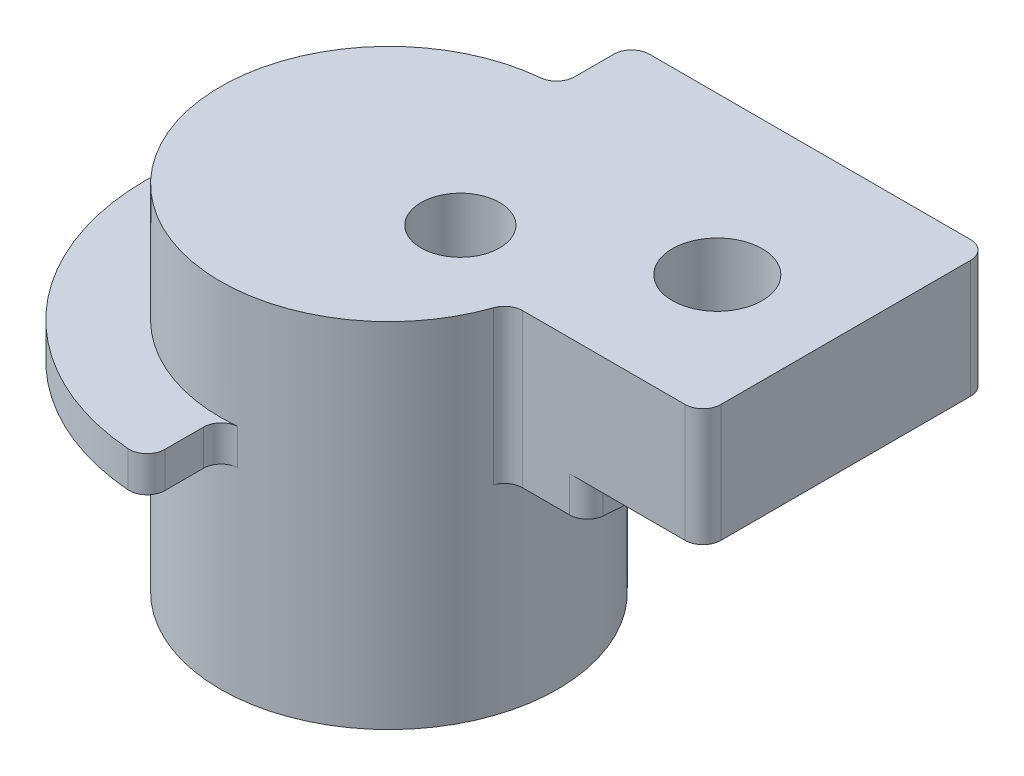
SolidWorks part; units mm, degrees
material "PET"
ref_plane "Front Plane" through (0, 0, 0) normal (1, 0, 0) x (0, 1, 0)
ref_plane "Top Plane" through (0, 0, 0) normal (0, 0, 1) x (0, 1, 0)
ref_plane "Right Plane" through (0, 0, 0) normal (0, 1, 0) x (-1, 0, 0)
sketch "Sketch2" plane through (0, 0, 0) normal (0, 0, 1) x (0, 1, 0)
  line L0 (0, 7.5) -> (0, -7.5) construction
  line L1 (15.7163, -7.5) -> (-15.7163, -7.5)
  line L2 (15.7163, -7.5) -> (15.7163, 7.5)
  line L3 (15.7163, 7.5) -> (-15.7163, 7.5)
  line L4 (-15.7163, -7.5) -> (-15.7163, 7.5)
  line L5 (15.7163, -7.5) -> (-15.7163, 7.5) construction
  line L6 (15.7163, 7.5) -> (-15.7163, -7.5) construction
  line L11 (-10.4775, 10.795) -> (-8.89, 10.795)
  line L12 (-10.4775, 10.795) -> (-10.4775, -10.795)
  line L19 (-10.4775, -10.795) -> (-8.89, -10.795)
  line L20 (-8.89, 10.795) -> (-8.89, -10.795)
  line L21 (10.4775, -10.795) -> (8.89, -10.795)
  line L22 (8.89, 10.795) -> (8.89, -10.795)
  line L23 (10.4775, 10.795) -> (8.89, 10.795)
  line L24 (10.4775, 10.795) -> (10.4775, -10.795)
  line L25 (-15.7163, 0) -> (15.7163, 0)
  point P0 (0, 0)
  point P6 (0, 0)
  point P11 (0, 0)
  point P16 (-10.4775, 0)
  dimension "D1" = 15
  dimension "D2" = 31.4325
  dimension "D5" = 1.5875
  dimension "D6" = 21.59
  dimension "D7" = 8.89
revolve "Revolve2" add sketch "Sketch2" angle 360 about L25 region at (-3.75, 13.0969, 0) region at (-3.75, 9.6838, 0) region at (-3.75, 0, 0) region at (-9.1475, 9.6838, 0) region at (-3.75, -9.6838, 0) region at (-3.75, -13.0969, 0) region at (-9.1475, -9.6838, 0)
sketch "Sketch3" plane through (0, 0, 0) normal (0, 1, 0) x (-1, 0, 0)
  circle A0 centre (0, 0) radius 11.3381
extrude "Cut-Extrude1" cut sketch "Sketch3" against normal blind 21.336
sketch "Sketch5" plane through (0, 15.7163, 0) normal (0, 1, 0) x (-1, 0, 0)
  line L5 (0, -10.795) -> (-15.875, -10.795)
  line L6 (0, -10.795) -> (0, 1.905)
  line L7 (0, 1.905) -> (-15.875, 1.905)
  line L8 (-15.875, -10.795) -> (-15.875, 1.905)
  circle A0 centre (-3.175, 0) radius 1.75
  circle A1 centre (0, 0) radius 7.5 construction
  circle A2 centre (0, 0) radius 7.5 construction
  circle A3 centre (-3.175, 0) radius 3.35 construction
  circle A9 centre (0, 0) radius 7.5
  circle A10 centre (-10.795, -3.81) radius 2
  circle A13 centre (0, 0) radius 10.795 construction
  circle A14 centre (-10.795, -3.81) radius 3.6 construction
  circle A15 centre (0, 0) radius 10.541 construction
  point P4 (7.5, 0)
  point P13 (-3.175, 1.75)
  point P15 (-3.175, 3.35)
  point P20 (-8.795, -3.81)
  point P21 (-7.195, -3.81)
  circle M7 centre (0, 0) radius 7.5
  dimension "D1" = 3.5
  dimension "D8" = 1.6
  dimension "D3" = 4
  dimension "D7" = 15.875
  dimension "D10" = 21.082
  dimension "D2" = 3.175
  dimension "D4" = 7.62
  dimension "D5" = 1.6
  dimension "D6" = 12.7
  dimension "D9" = 3.81
  dimension "5" = 0
extrude "Cut-Extrude3" cut sketch "Sketch5" against normal blind 27.432 contours A0 region at (3.175, 15.7163, 0)
extrude "Boss-Extrude2" add sketch "Sketch5<3>" against normal up to surface (5.2387 mm away) contours L8 A10 M7 region at (9.7265, 15.7163, -5.5154) up to face at (7.5, 10.4775, 0)
sketch "Sketch5<3>" plane through (0, 15.7163, 0) normal (0, 1, 0) x (-1, 0, 0) same geometry as "Sketch5"
fillet "Fillet1" radius 0.7937 5 edges at (0, 13.0969, -10.795) (0, 13.0969, -7.5) (15.875, 13.0969, -10.795) (7.254, 13.0969, 1.905) (15.875, 13.0969, 1.905)
sketch "Sketch6" plane through (0, 10.4775, 0) normal (0, 1, 0) x (-1, 0, 0)
  line L0 (0, 7.5) -> (0, 10.795)
  line L3 (0, -8.2557) -> (0, -10.0013)
  line L4 (-10.6256, 1.905) -> (-7.8424, 1.905)
  line L5 (0, -8.2557) -> (0, -10.0013)
  line L6 (-10.6256, 1.905) -> (-7.8424, 1.905)
  arc A0 (0.7178, -7.4656) -> (-7.0918, 2.4405) centre (0, 0) ccw construction
  arc A1 (-0.6251, -10.7769) -> (-10.6256, 1.905) centre (0, 0) ccw construction
  arc A7 (0.7178, -7.4656) -> (-7.0918, 2.4405) centre (0, 0) ccw
  arc A8 (0.7178, -7.4656) -> (0, -8.2557) centre (0.7938, -8.2557) ccw
  arc A9 (-0.6251, -10.7769) -> (0, -10.0013) centre (-0.7937, -10.0013) ccw
  arc A10 (-0.6251, -10.7769) -> (-10.6256, 1.905) centre (0, 0) ccw
  arc A11 (-7.8424, 1.905) -> (-7.0918, 2.4405) centre (-7.8424, 2.6987) ccw
  arc A12 (0.7178, -7.4656) -> (-7.0918, 2.4405) centre (0, 0) ccw
  arc A13 (0.7178, -7.4656) -> (0, -8.2557) centre (0.7938, -8.2557) ccw
  arc A14 (-0.6251, -10.7769) -> (0, -10.0013) centre (-0.7937, -10.0013) ccw
  arc A15 (-0.6251, -10.7769) -> (-10.6256, 1.905) centre (0, 0) ccw
  arc A16 (-7.8424, 1.905) -> (-7.0918, 2.4405) centre (-7.8424, 2.6987) ccw
  arc M8 (-7.0918, 2.4405) -> (0.7178, -7.4656) centre (0, 0) cw
  arc M12 (-0.6251, -10.7769) -> (-10.6256, 1.905) centre (0, 0) ccw
  line M13 (-10.6256, 1.905) -> (-7.8424, 1.905)
  arc M14 (-7.8424, 1.905) -> (-7.0918, 2.4405) centre (-7.8424, 2.6987) ccw
  dimension "D1" = 0
extrude "Cut-Extrude4" cut sketch "Sketch6" against normal blind 14.224 contours L0 M8 M12 M13 M14 region at (5.3913, 10.4775, 6.6538)
fillet "Fillet2" radius 0.7937 3 edges at (10.6256, 9.6838, 1.905) (0, 9.6838, 7.5) (0, 9.6838, 10.795)
